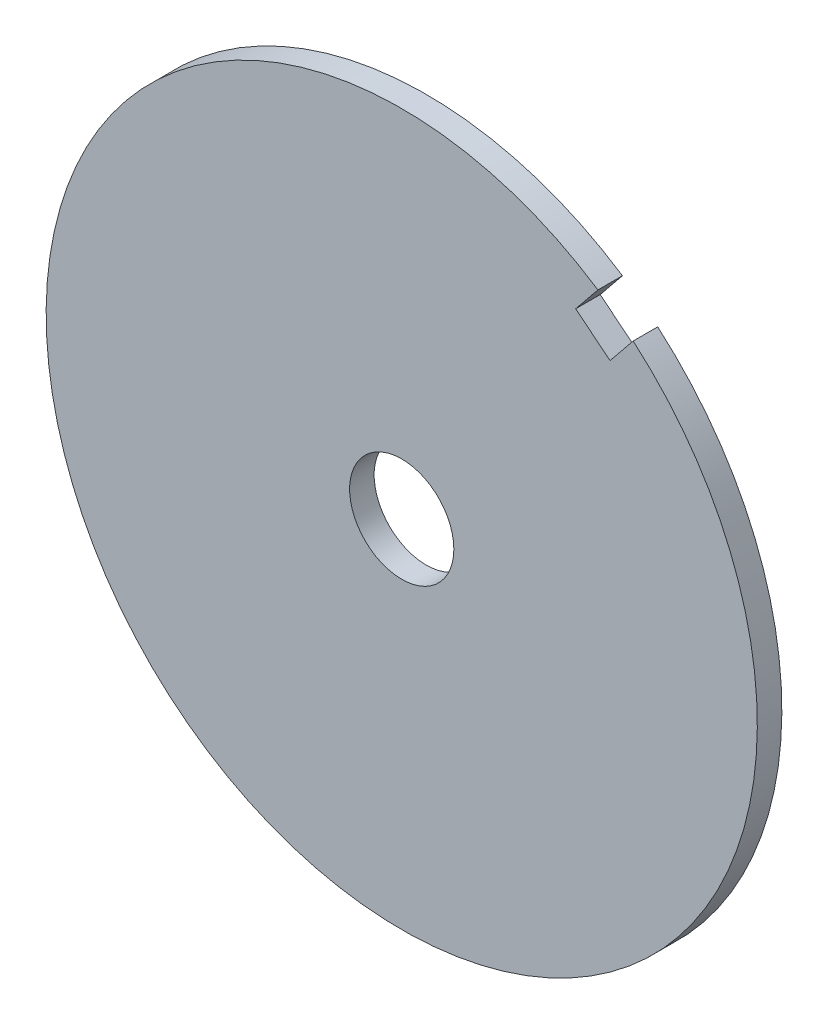
SolidWorks part; units mm, degrees
ref_plane "Front Plane" through (0, 0, 0) normal (0, 0, 1) x (1, 0, 0)
ref_plane "Top Plane" through (0, 0, 0) normal (0, 1, 0) x (1, 0, 0)
ref_plane "Right Plane" through (0, 0, 0) normal (1, 0, 0) x (0, 0, -1)
sketch "Sketch1" plane through (0, 0, 3372.7778) normal (0, 0, 1) x (1, 0, 0)
  circle A0 centre (0, 0) radius 92.075
  dimension "D1" = 184.15
extrude "Boss-Extrude1" add sketch "Sketch1" along normal blind 6.35
sketch "Sketch2" plane through (0, 0, 3379.1278) normal (0, 0, 1) x (1, 0, 0)
  circle A0 centre (0, 0) radius 13.4938
  dimension "D1" = 26.9875
extrude "Cut-Extrude1" cut sketch "Sketch2" against normal up to next
sketch "Sketch3" plane through (0, 0, 3379.1278) normal (0, 0, 1) x (1, 0, 0)
  line L0 (50.7995, 76.7933) -> (45.0508, 69.7006)
  line L1 (45.0508, 69.7006) -> (53.9303, 62.5035)
  line L2 (53.9303, 62.5035) -> (59.9279, 69.9032)
  line L3 (149.5292, 194.5687) -> (76.0344, 103.8934) construction
  line L4 (80.9675, 99.895) -> (154.4623, 190.5703) construction
  circle A0 centre (0, 0) radius 92.075 construction
  dimension "D1" = 2.54
  dimension "D2" = 2.54
  dimension "D3" = 9.525
extrude "Cut-Extrude2" cut sketch "Sketch3" against normal through all and the other way through all
